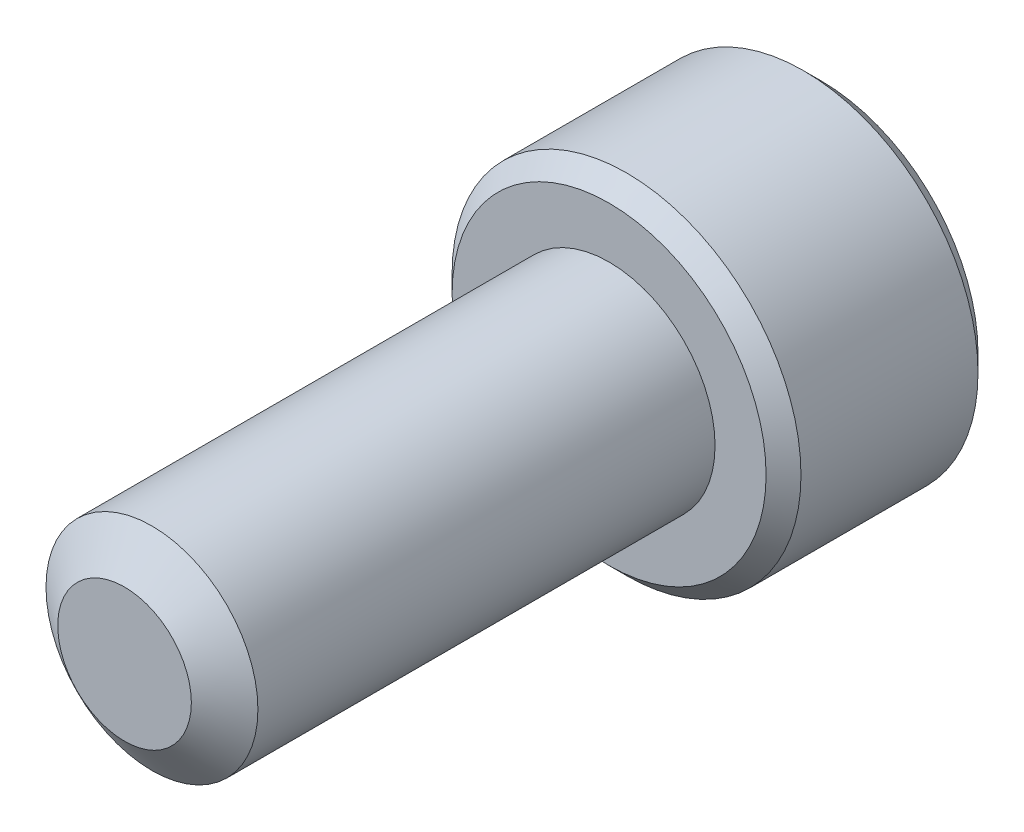
SolidWorks part; units mm, degrees
ref_plane "Front Plane" through (0, 0, 0) normal (0, 0, 1) x (1, 0, 0)
ref_plane "Top Plane" through (0, 0, 0) normal (0, 1, 0) x (1, 0, 0)
ref_plane "Right Plane" through (0, 0, 0) normal (1, 0, 0) x (0, 0, -1)
sketch "Sketch1" plane through (0, 0, 0) normal (0, 0, 1) x (1, 0, 0)
  circle A0 centre (0, 0) radius 2.0828
  dimension "OD" = 4.1656
extrude "Extrude1" add sketch "Sketch1" against normal blind 9.525
sketch "Sketch2" plane through (0, 0, 0) normal (0, 0, 1) x (1, 0, 0)
  circle A0 centre (0, 0) radius 2.0828 construction
  circle A1 centre (0, 0) radius 2.0828
curve "Helix/Spiral1" pitch 0.7937 height 10.3188 turns 13 parameters "pitch"=0.7937
sketch "Sketch3" plane through (0, 0, 0) normal (1, 0, 0) x (0, 0, -1)
  line L0 (-0.6945, 2.0828) -> (-0.3969, 1.5672)
  line L1 (-0.3969, 1.5672) -> (-0.2977, 1.5672)
  line L2 (-0.2977, 1.5672) -> (0, 2.0828)
  line L3 (-0.6945, 2.0828) -> (0, 2.0828)
  line L4 (-0.3473, 2.0828) -> (-0.3473, 1.5672) construction
  line L5 (-0.5457, 1.825) -> (-0.1488, 1.825) construction
  line L6 (0, 2.0828) -> (0, -2.0828) construction
  dimension "D1" = 0.0992
  dimension "D2" = 0.3969
  dimension "D3" = 60
sweep "Cut-Sweep1" [suppressed] cut profiles "Sketch3" path "Helix/Spiral1"
sketch "Sketch4" plane through (0, 0, 0) normal (1, 0, 0) x (0, 0, -1)
  line L0 (0.5388, 2.0828) -> (0, 1.3132)
  line L1 (0, 1.3132) -> (0, 2.0828)
  line L2 (0.5388, 2.0828) -> (0, 2.0828)
  line L3 (-0.6945, 2.0828) -> (0, 2.0828) construction
  line L4 (0, 0) -> (7.0209, 0) construction
  dimension "D1" = 55
  dimension "D2" = 0.254
revolve "Cut-Revolve1" cut sketch "Sketch4" angle 360 about L4
sketch "Sketch5" [suppressed] plane through (0, 0, 0) normal (1, 0, 0) x (0, 0, -1)
  line L0 (9.525, -1.5805) -> (9.525, 1.4861) construction
  line L1 (9.525, 2.2098) -> (87.4327, 2.2098)
  line L2 (9.525, 2.2098) -> (9.525, 0)
  line L3 (9.525, 0) -> (87.3125, 0)
  line L4 (87.3125, 1.8796) -> (87.3125, 0)
  line L5 (87.4327, 2.2098) -> (87.3125, 1.8796)
  line L6 (0, 0) -> (9.9695, 0) construction
  point P3 (87.3125, 2.2098)
  point P10 (87.3125, 2.2098)
  dimension "D1" = 0.3302
  dimension "Thread min" = 87.3125
  dimension "D2" = 0.127
  dimension "D3" = 20
revolve "partially thread" [suppressed] add sketch "Sketch5" angle 360 about L6
sketch "Sketch6" plane through (0, 0, -9.525) normal (0, 0, -1) x (-1, 0, 0)
  circle A0 centre (0, 0) radius 3.429
  dimension "head dia" = 6.858
extrude "Extrude2" add sketch "Sketch6" along normal blind 4.1656
sketch "Sketch7" plane through (0, 0, -13.6906) normal (0, 0, -1) x (-1, 0, 0)
  line L1 (0, 2.0622) -> (-1.7859, 1.0311)
  line L2 (-1.7859, 1.0311) -> (-1.7859, -1.0311)
  line L3 (-1.7859, -1.0311) -> (0, -2.0622)
  line L4 (0, -2.0622) -> (1.7859, -1.0311)
  line L5 (1.7859, -1.0311) -> (1.7859, 1.0311)
  line L6 (1.7859, 1.0311) -> (0, 2.0622)
  circle A0 centre (0, 0) radius 1.7859 construction
  dimension "hex dia" = 3.5719
extrude "Cut-Extrude1" cut sketch "Sketch7" against normal blind 2.6789
sketch "Sketch8" plane through (0, 0, -13.6906) normal (0, 0, -1) x (-1, 0, 0)
  circle A0 centre (0, 0) radius 2.0622
extrude "Cut-Extrude2" cut sketch "Sketch8" against normal through all draft 45
chamfer "Chamfer1" distance 0.3429 angle 45 2 edges at (-3.429, 0, -13.6906) (-3.429, 0, -9.525)
sketch "Sketch9" plane through (0, 0, 0) normal (1, 0, 0) x (0, 0, -1)
  line L0 (0, 2.0828) -> (0, -2.0828) construction
  line L1 (4.3656, 2.0828) -> (4.3656, -2.0828) construction
  dimension "D1" = 4.3656
equation "\"D3@Helix/Spiral1\" = \"screw length@Extrude1\"+\"pitch@Helix/Spiral1\""
equation "\"D1@Sketch3\" = \"pitch@Helix/Spiral1\"*.125"
equation "\"D2@Sketch3\" = \"pitch@Helix/Spiral1\"*.5"
equation "\"D1@Cut-Extrude1\" = \"hex dia@Sketch7\"*.75"
equation "\"D1@Chamfer1\" = \"head dia@Sketch6\"*.05"
equation "\"D1@Sketch9\" = \"pitch@Helix/Spiral1\"*5.5"
